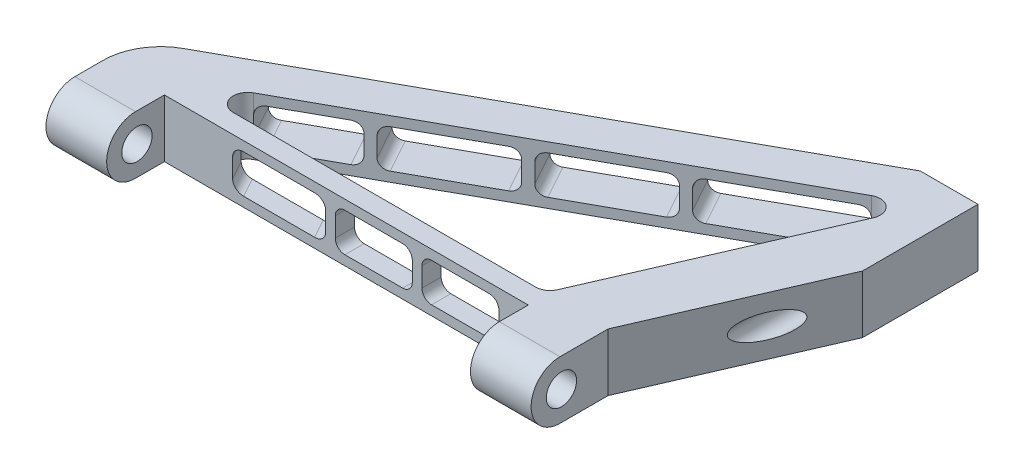
SolidWorks part; units mm, degrees
other "Markup1"
sketch "Sketch9" plane through (-9.525, 19.05, 0) normal (-0.761, 0.4779, -0.4388) x (-0.0596, 0.622, 0.7808)
material "6061-T6 (SS)"
ref_plane "Front Plane" through (0, 0, 0) normal (0, 0, 1) x (1, 0, 0)
ref_plane "Top Plane" through (0, 0, 0) normal (0, 1, 0) x (1, 0, 0)
ref_plane "Right Plane" through (0, 0, 0) normal (1, 0, 0) x (0, 0, -1)
sketch "Sketch1" plane through (0, 0, 0) normal (0, 1, 0) x (1, 0, 0)
  line L0 (0, 0) -> (0, -122) construction
  line L1 (0, 0) -> (165.875, 0) construction
  line L2 (165.875, 0) -> (165.875, -38.1) construction
  line L3 (156.35, 0) -> (175.4, 0)
  line L4 (175.4, 0) -> (175.4, -38.1)
  line L5 (0, -122) -> (0, -112) construction
  line L7 (10, -122) -> (-10, -122)
  line L12 (10, -102.95) -> (10, -122)
  line L13 (-76.2946, -112) -> (175.6699, -112) construction
  line L14 (140, -122) -> (-10, -122) construction
  line L15 (150, -122) -> (130, -122)
  line L16 (130, -122) -> (130, -102.95)
  line L17 (150, -122) -> (150, -96.6)
  line L20 (150, -96.6) -> (175.4, -38.1)
  line L21 (10, -102.95) -> (130, -102.95)
  line L24 (130, -102.95) -> (130, -54.7662) construction
  line L27 (161.9925, -21.1474) -> (130.4761, -93.7342)
  line L28 (155.3191, -15.083) -> (24.0709, -87.6699)
  line L29 (26.3758, -96.6) -> (126.1076, -96.6)
  line L31 (-10, -92) -> (156.35, 0)
  line L32 (-10, -122) -> (-10, -92)
  line L34 (165.875, 0) -> (165.875, 30) construction
  arc A7 (26.3758, -96.6) -> (24.0709, -87.6699) centre (26.3758, -91.8375) cw
  arc A8 (126.1076, -96.6) -> (130.4761, -93.7342) centre (126.1076, -91.8375) ccw
  arc A9 (155.3191, -15.083) -> (161.9925, -21.1474) centre (157.624, -19.2506) cw
  point P7 (165.875, 0)
  point P11 (70, -96.6)
  point P13 (0, -112)
  point P16 (0, -122)
  point P20 (140, -122)
  point P28 (129.2318, -96.6)
  point P36 (165.875, -35.3491)
  point P45 (162.8454, -13.5799)
  point P48 (22.05, -96.6)
  dimension "D12" = 30
  dimension "D13" = 19.05
  dimension "D14" = 12.7
  dimension "D17" = 6.35
  dimension "D18" = 4.7625
  dimension "D15" = 4.7625
  dimension "D2" = 15.875
  dimension "D3" = 38.1
  dimension "D4" = 38.1
  dimension "D5" = 112
  dimension "D6" = 20
  dimension "D7" = 140
  dimension "D8" = 20
  dimension "D9" = 10
  dimension "D10" = 19.05
  dimension "D11" = 19.05
  dimension "D16" = 30
extrude "Boss-Extrude1" add sketch "Sketch1" along normal blind 19.05 contours L12 L21 L16 L15 L17 L20 L4 L3 L7 region at (165.875, 0, 2.2194)
sketch "Sketch3" plane through (0, 0, 0) normal (0, 0, -1) x (-1, 0, 0)
  line L0 (-156.35, 19.05) -> (-175.4, 19.05) construction
  line L1 (-175.4, 19.05) -> (-175.4, 0) construction
  circle A0 centre (-165.875, 9.525) radius 3.9687
  dimension "D1" = 7.9375
  dimension "D3" = 9.525
  dimension "D2" = 9.525
extrude "Cut-Extrude1" cut sketch "Sketch3" against normal up to next
fillet "Fillet1" 2 edges at (0, 19.05, 122) (0, 0, 122) type full round first side face at (97.0136, 19.05, 83.6909) second side face at (97.0136, 0, 83.6909) middle face at (0, 9.525, 122)
sketch "Sketch6" plane through (150, 0, 0) normal (1, 0, 0) x (0, 0, -1)
  line L1 (-112, 0) -> (-112, 19.05) construction
  line L2 (-122, 19.05) -> (-96.6, 19.05) construction
  circle A0 centre (-112, 9.525) radius 5
  point P4 (-112, 9.525)
  point P5 (-112, 0)
  dimension "D1" = 10
extrude "Cut-Extrude3" cut sketch "Sketch6" against normal through all
fillet "Fillet2" 2 edges at (140, 19.05, 122) (140, 0, 122) type full round first side face at (97.0136, 19.05, 81.9591) second side face at (97.0136, 0, 81.9591) middle face at (140, 9.525, 122)
fillet "Fillet6" radius 19.05 1 edges at (-10, 9.525, 92)
sketch "Sketch8" [suppressed] plane through (0, 19.05, 0) normal (0, 1, 0) x (1, 0, 0)
  line L4 (124.165, -36.1434) -> (43.4987, -83.1988) construction
  line L10 (160.5971, -158.3087) -> (103.1838, -57.8355)
  line L11 (130.8738, -89.8648) -> (115.3014, -62.613)
  line L12 (160.1788, -156.7334) -> (160.1788, 27.2514)
  line L13 (126.0432, -94.615) -> (128.1172, -94.615)
  line L14 (136.525, -92.075) -> (161.192, -5.7404) construction
  line L15 (81.7133, -27.9414) -> (112.9323, -82.5745) construction
  line L16 (156.3688, -22.6219) -> (156.3688, 0) construction
  line L17 (9.525, -98.425) -> (117.475, -98.425) construction
  line L18 (108.2246, -66.6568) -> (123.2866, -93.0152)
  line L19 (109.406, -62.3249) -> (110.9695, -61.4315)
  line L20 (107.5158, -59.0169) -> (147.6154, -36.1028)
  line L21 (149.093, -34.2184) -> (166.4066, 26.3792)
  line L34 (144.6213, -12.095) -> (144.6213, -17.9761)
  line L35 (122.2453, -32.8524) -> (41.579, -79.9078)
  line L36 (143.046, -20.7186) -> (113.4191, -38.001)
  line L37 (148.4313, 0) -> (148.4313, -50.4031) construction
  line L38 (98.8839, -33.2473) -> (3.8265, -88.6975)
  line L39 (109.0769, -36.8583) -> (106.5172, -32.4703)
  line L40 (105.7859, -38.778) -> (103.2262, -34.39)
  line L41 (104.6431, -43.1203) -> (17.108, -94.1825)
  line L45 (137.6708, -10.6216) -> (1.846, -89.8528)
  line L46 (-5.715, -103.0168) -> (-5.715, -104.14)
  line L47 (-5.715, -104.14) -> (5.715, -104.14)
  line L48 (5.715, -104.14) -> (5.715, -94.615)
  line L49 (5.715, -94.615) -> (121.285, -94.615)
  line L50 (121.285, -94.615) -> (121.285, -104.14)
  line L51 (121.285, -104.14) -> (132.715, -104.14)
  line L52 (132.715, -104.14) -> (132.715, -91.5414)
  line L53 (132.715, -91.5414) -> (157.5286, -4.6937)
  line L55 (157.7528, -3.81) -> (145.0012, -3.81)
  line L57 (139.8465, -9.3525) -> (107.6599, -28.128)
  line L61 (5.4262, -94.615) -> (15.5082, -94.615)
  line L65 (132.715, -91.5414) -> (157.5286, -4.6937)
  arc A6 (123.2866, -93.0152) -> (126.0432, -94.615) centre (126.0432, -91.44) ccw
  arc A7 (130.8738, -89.8648) -> (128.1172, -94.615) centre (128.1172, -91.44) cw
  arc A8 (110.9695, -61.4315) -> (115.3014, -62.613) centre (112.5447, -64.1882) cw
  arc A9 (109.406, -62.3249) -> (108.2246, -66.6568) centre (110.9813, -65.0816) ccw
  arc A10 (107.5158, -59.0169) -> (103.1838, -57.8355) centre (105.9405, -56.2603) cw
  arc A11 (147.6154, -36.1028) -> (149.093, -34.2184) centre (146.0402, -33.3462) ccw
  arc A12 (160.5971, -158.3087) -> (160.1788, -156.7334) centre (163.3538, -156.7334) cw
  arc A13 (160.1788, 27.2514) -> (166.4066, 26.3792) centre (163.3538, 27.2514) cw
  arc A14 (144.6213, -12.095) -> (139.8465, -9.3525) centre (141.4462, -12.095) ccw
  arc A15 (17.108, -94.1825) -> (15.5082, -94.615) centre (15.5082, -91.44) cw
  arc A16 (3.8265, -88.6975) -> (5.4262, -94.615) centre (5.4262, -91.44) ccw
  arc A17 (105.7859, -38.778) -> (104.6431, -43.1203) centre (103.0434, -40.3778) cw
  arc A18 (103.2262, -34.39) -> (98.8839, -33.2473) centre (100.4837, -35.9898) ccw
  arc A19 (106.5172, -32.4703) -> (107.6599, -28.128) centre (109.2597, -30.8705) cw
  arc A20 (109.0769, -36.8583) -> (113.4191, -38.001) centre (111.8194, -35.2585) ccw
  arc A21 (144.6213, -17.9761) -> (143.046, -20.7186) centre (141.4462, -17.9761) cw
  arc A26 (1.846, -89.8528) -> (-5.715, -103.0168) centre (9.525, -103.0168) ccw
  arc A28 (157.5286, -4.6937) -> (157.7528, -3.81) centre (142.875, -0.507) ccw
  arc A29 (137.6708, -10.6216) -> (145.0012, -3.81) centre (126.1523, 9.1243) ccw
  dimension "D4" = 3.81
  dimension "D5" = 3.175
  dimension "D3" = 3.81
  dimension "D6" = 3.175
  dimension "D7" = 3.81
  dimension "D10" = 3.175
  dimension "D2" = 3.81
  dimension "D8" = 3.81
  dimension "D9" = 3.81
  dimension "D11" = 3.81
  dimension "D12" = 3.81
  dimension "D13" = 3.81
  dimension "D15" = 43.18
  dimension "D16" = 48.7737
extrude "Cut-Extrude4" [suppressed] cut sketch "Sketch8" against normal blind 12.7 contours A21 L34 A14 L57 A19 L39 A20 L36 | L40 A18 L38 A16 L61 A15 L41 A17 | A13 L12 A12 L10 A10 L20 A11 L21 | L19 A9 L18 A6 L13 A7 L11 A8
thread "Thread2" pitch 1.0583 method cut profile "Thread Profile2" start angle 0, offset 0, length 28.575, pitch 1.0583, diameter 7.9375
ref_plane "Plane2" through (169.8437, 9.525, 0) normal (0, -1, 0) x (1, 0, 0)
sketch "Thread Profile2" plane through (169.8437, 9.525, 0) normal (0, -1, 0) x (1, 0, 0)
  line L0 (0, 0) -> (0, 1.0583) construction
  line L1 (0, 0) -> (0.5728, 0.3307)
  line L2 (0.5728, 0.3307) -> (0.5728, 0.463)
  line L3 (0.5728, 0.463) -> (0, 0.7937)
  line L4 (0.5728, 0.3969) -> (0, 0.3969) construction
  line L11 (0, 0) -> (0, 0.7937)
  point P2 (0, 0)
  dimension "Pitch" = 1.0583
  dimension "Profile_Angle" = 60
  dimension "Profile_Land" = 0.1323
  dimension "Profile_Height" = 0.5728
sketch "Sketch10" plane through (0, 0, 0) normal (1, 0, 0) x (0, 0, -1)
  point P0 (-112, 9.525)
sketch3d "3DSketch2"
  line L0 (0, 9.525, 112) -> (167.6024, 9.525, 112) construction
  circle A0 centre (150, 9.525, 112) radius 5 construction
  circle A1 centre (-10, 9.525, 112) radius 5 construction
  point P5 (155, 9.525, 112)
  point P9 (-5, 9.525, 112)
sketch "Sketch11" plane through (36.6209, 0, 66.2162) normal (-0.484, 0, -0.8751) x (-0.8751, 0, 0.484)
  line L0 (21.3821, 12.7) -> (21.3821, 6.35)
  line L1 (-40.5875, 3.175) -> (-11.8187, 3.175)
  line L2 (-43.7625, 12.7) -> (-43.7625, 6.35)
  line L3 (18.2071, 15.875) -> (-2.2937, 15.875)
  line L4 (-128.6179, 0) -> (21.3652, 0)
  line L5 (-128.6179, 19.05) -> (-128.6179, 0)
  line L6 (21.3652, 19.05) -> (-128.6179, 19.05)
  line L7 (21.3652, 0) -> (21.3652, 19.05)
  line L9 (-128.6179, 12.7) -> (-128.6179, 6.35)
  line L13 (-125.4429, 3.175) -> (-88.4062, 3.175)
  line L15 (18.2071, 15.875) -> (-125.4429, 15.875) construction
  line L16 (-125.4429, 3.175) -> (18.2071, 3.175) construction
  line L17 (-46.9375, 12.7) -> (-46.9375, 6.35)
  line L18 (-128.6179, 19.05) -> (-128.6179, 0) construction
  line L19 (21.3821, 19.05) -> (-128.6179, 19.05) construction
  line L20 (21.3821, 19.05) -> (21.3821, 0) construction
  line L21 (-128.6179, 0) -> (21.3821, 0) construction
  line L22 (18.2071, 15.875) -> (18.2071, 3.175) construction
  line L23 (-125.4429, 15.875) -> (-125.4429, 3.175) construction
  line L24 (-50.1125, 15.875) -> (-78.8812, 15.875)
  line L25 (-78.8812, 3.175) -> (-50.1125, 3.175)
  line L26 (-11.8187, 15.875) -> (-40.5875, 15.875)
  line L27 (-8.6437, 12.7) -> (-8.6437, 6.35)
  line L28 (-85.2312, 12.7) -> (-85.2312, 6.35)
  line L29 (-5.4687, 12.7) -> (-5.4687, 6.35)
  line L30 (-82.0562, 12.7) -> (-82.0562, 6.35)
  line L31 (-88.4062, 15.875) -> (-125.4429, 15.875)
  line L32 (-2.2937, 3.175) -> (18.2071, 3.175)
  arc A0 (18.2071, 3.175) -> (21.3821, 6.35) centre (18.2071, 6.35) ccw
  arc A1 (18.2071, 15.875) -> (21.3821, 12.7) centre (18.2071, 12.7) cw
  arc A2 (-5.4687, 12.7) -> (-2.2937, 15.875) centre (-2.2937, 12.7) cw
  arc A3 (-5.4687, 6.35) -> (-2.2937, 3.175) centre (-2.2937, 6.35) ccw
  arc A4 (-8.6437, 6.35) -> (-11.8187, 3.175) centre (-11.8187, 6.35) cw
  arc A5 (-8.6437, 12.7) -> (-11.8187, 15.875) centre (-11.8187, 12.7) ccw
  arc A6 (-43.7625, 12.7) -> (-40.5875, 15.875) centre (-40.5875, 12.7) cw
  arc A7 (-43.7625, 6.35) -> (-40.5875, 3.175) centre (-40.5875, 6.35) ccw
  arc A8 (-46.9375, 6.35) -> (-50.1125, 3.175) centre (-50.1125, 6.35) cw
  arc A9 (-46.9375, 12.7) -> (-50.1125, 15.875) centre (-50.1125, 12.7) ccw
  arc A10 (-82.0562, 12.7) -> (-78.8812, 15.875) centre (-78.8812, 12.7) cw
  arc A11 (-82.0562, 6.35) -> (-78.8812, 3.175) centre (-78.8812, 6.35) ccw
  arc A12 (-125.4429, 3.175) -> (-128.6179, 6.35) centre (-125.4429, 6.35) cw
  arc A13 (-85.2312, 6.35) -> (-88.4062, 3.175) centre (-88.4062, 6.35) cw
  arc A14 (-85.2312, 12.7) -> (-88.4062, 15.875) centre (-88.4062, 12.7) ccw
  arc A15 (-125.4429, 15.875) -> (-128.6179, 12.7) centre (-125.4429, 12.7) ccw
  point P20 (21.3821, 3.175)
  point P31 (21.3821, 15.875)
  dimension "D5" = 3.175
  dimension "D2" = 150
  dimension "D4" = 12.7
  dimension "D1" = 0
  dimension "D3" = 3.175
extrude "Cut-Extrude5" cut sketch "Sketch11" against normal blind 24.175
sketch "Sketch12" plane through (36.6209, 0, 66.2162) normal (-0.484, 0, -0.8751) x (-0.8751, 0, 0.484)
  line L8 (-2.2937, 3.175) -> (18.2071, 3.175) construction
  line L9 (-5.4687, 12.7) -> (-5.4687, 6.35) construction
  line L10 (18.2071, 15.875) -> (-2.2937, 15.875) construction
  line L11 (-2.2937, 3.175) -> (18.2071, 3.175)
  line L12 (-5.4687, 12.7) -> (-5.4687, 6.35)
  line L13 (18.2071, 15.875) -> (-2.2937, 15.875)
  line L14 (21.3821, 6.35) -> (21.3821, 12.7) construction
  line L15 (21.3821, 6.35) -> (21.3821, 12.7)
  arc A8 (-5.4687, 6.35) -> (-2.2937, 3.175) centre (-2.2937, 6.35) ccw construction
  arc A9 (-2.2937, 15.875) -> (-5.4687, 12.7) centre (-2.2937, 12.7) ccw construction
  arc A10 (-5.4687, 6.35) -> (-2.2937, 3.175) centre (-2.2937, 6.35) ccw
  arc A11 (-2.2937, 15.875) -> (-5.4687, 12.7) centre (-2.2937, 12.7) ccw
  arc A12 (21.3821, 12.7) -> (18.2071, 15.875) centre (18.2071, 12.7) ccw construction
  arc A13 (18.2071, 3.175) -> (21.3821, 6.35) centre (18.2071, 6.35) ccw construction
  arc A14 (18.2071, 3.175) -> (21.3821, 6.35) centre (18.2071, 6.35) ccw
  arc A15 (21.3821, 12.7) -> (18.2071, 15.875) centre (18.2071, 12.7) ccw
extrude "Cut-Extrude6" cut sketch "Sketch12" against normal blind 132
sketch "Sketch13" plane through (0, 0, 102.95) normal (0, 0, 1) x (1, 0, 0)
  line L4 (0, 9.525) -> (167.6024, 9.525) construction
  line L5 (69.536, 15.875) -> (88.586, 15.875)
  line L6 (66.361, 12.7) -> (66.361, 6.35)
  line L7 (69.536, 3.175) -> (88.586, 3.175)
  line L8 (91.761, 12.7) -> (91.761, 6.35)
  line L10 (94.941, 12.7) -> (94.941, 6.35)
  line L11 (98.116, 15.875) -> (117.166, 15.875)
  line L12 (120.341, 12.7) -> (120.341, 6.35)
  line L13 (98.116, 3.175) -> (117.166, 3.175)
  arc A4 (66.361, 6.35) -> (69.536, 3.175) centre (69.536, 6.35) ccw
  arc A5 (88.586, 3.175) -> (91.761, 6.35) centre (88.586, 6.35) ccw
  arc A6 (88.586, 15.875) -> (91.761, 12.7) centre (88.586, 12.7) cw
  arc A7 (69.536, 15.875) -> (66.361, 12.7) centre (69.536, 12.7) ccw
  arc A8 (98.116, 15.875) -> (94.941, 12.7) centre (98.116, 12.7) ccw
  arc A9 (94.941, 6.35) -> (98.116, 3.175) centre (98.116, 6.35) ccw
  arc A10 (117.166, 15.875) -> (120.341, 12.7) centre (117.166, 12.7) cw
  arc A11 (117.166, 3.175) -> (120.341, 6.35) centre (117.166, 6.35) ccw
  point P4 (66.361, 9.525)
  point P11 (66.361, 3.175)
  point P16 (91.761, 15.875)
  point P19 (66.361, 15.875)
  dimension "D4" = 3.175
  dimension "D1" = 12.7
  dimension "D3" = 25.4
  dimension "D5" = 2
extrude "Cut-Extrude7" cut sketch "Sketch13" against normal blind 23
move or copy body "Body-Move/Copy2" [suppressed] bodies to move or copy 105
move or copy body "Body-Move/Copy1" [suppressed] bodies to move or copy 105
